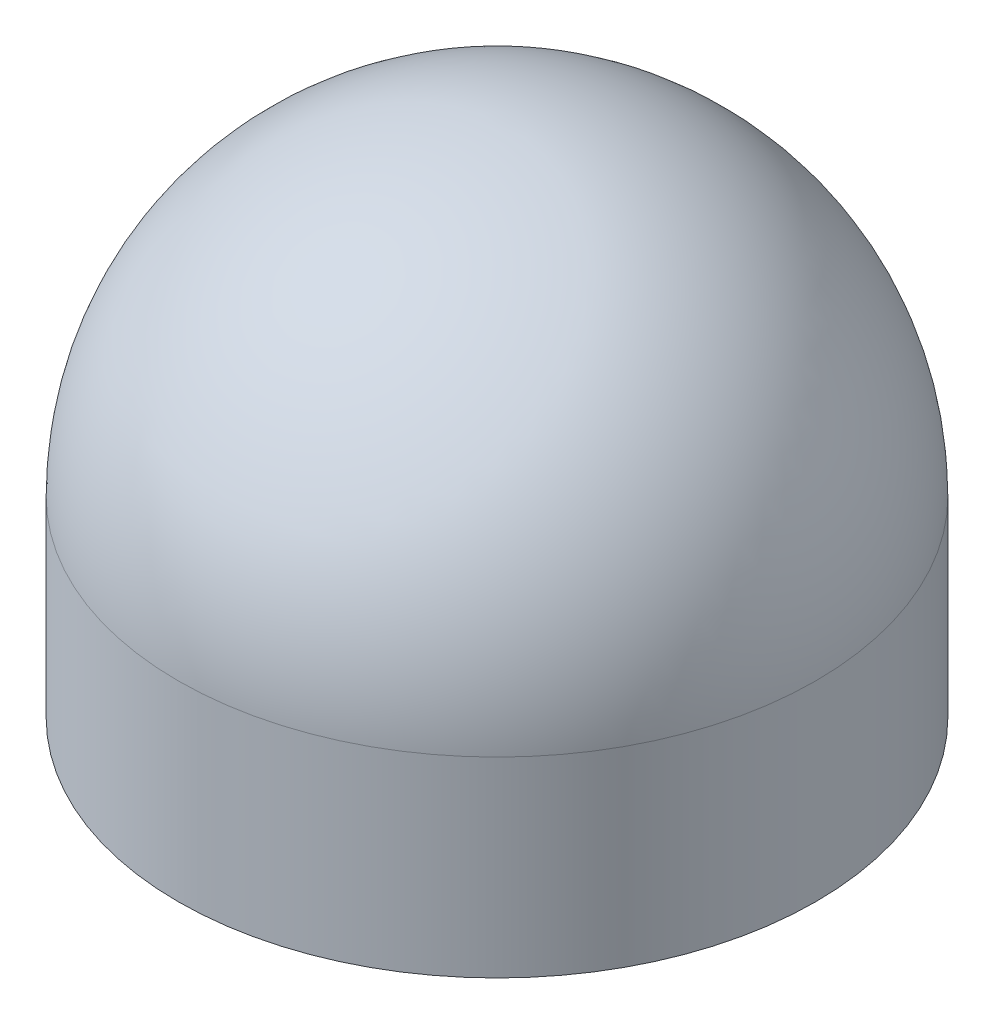
SolidWorks part; units mm, degrees
material "ABS"
ref_plane "Front Plane" through (0, 0, 0) normal (0, 0, 1) x (1, 0, 0)
ref_plane "Top Plane" through (0, 0, 0) normal (0, 1, 0) x (1, 0, 0)
ref_plane "Right Plane" through (0, 0, 0) normal (1, 0, 0) x (0, 0, -1)
sketch "Sketch1" plane through (0, 0, 0) normal (0, 1, 0) x (1, 0, 0)
  circle A0 centre (0, 0) radius 1.5
  dimension "D1" = 3
extrude "Boss-Extrude1" add sketch "Sketch1" along normal blind 0.9
dome "Dome1" faces to dome 1 distance 1.5 reverse direction no elliptical dome no face at (0, 0.9, 1.5) parameters "D1"=1.5
